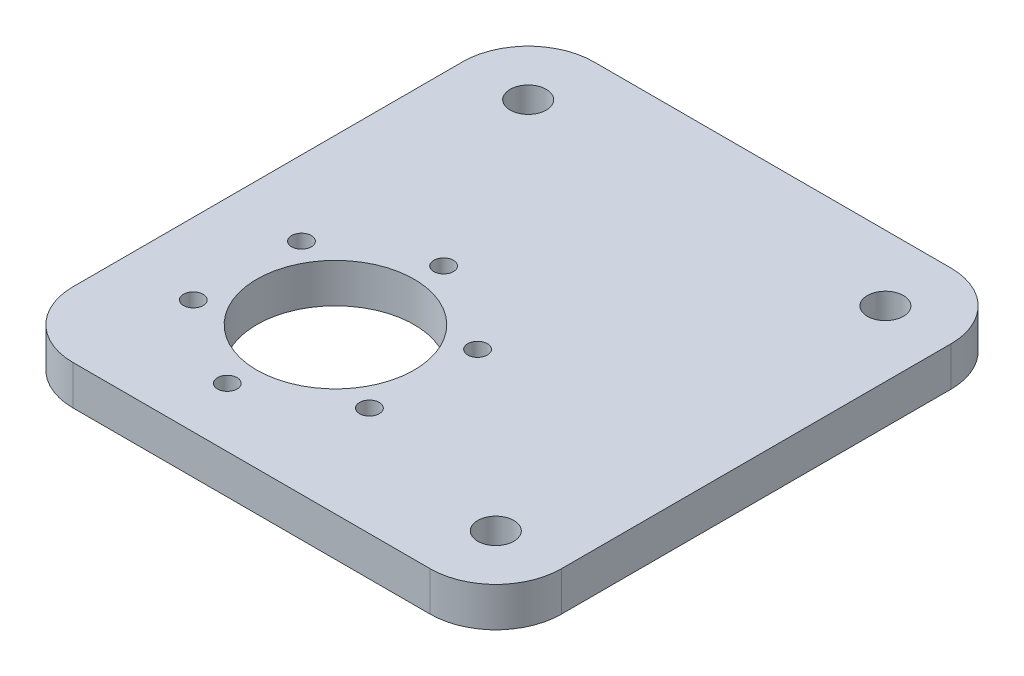
SolidWorks part; units mm, degrees
ref_plane "Front Plane" through (0, 0, 0) normal (0, 0, 1) x (1, 0, 0)
ref_plane "Top Plane" through (0, 0, 0) normal (0, 1, 0) x (1, 0, 0)
ref_plane "Right Plane" through (0, 0, 0) normal (1, 0, 0) x (0, 0, -1)
sketch "Sketch2" plane through (0, 0, 0) normal (0, 1, 0) x (1, 0, 0)
  line L1 (-18.6933, 53.5256) -> (55.7467, 53.5256)
  line L2 (-18.6933, 53.5256) -> (-18.6933, -25.8544)
  line L3 (-18.6933, -25.8544) -> (55.7467, -25.8544)
  line L4 (55.7467, 53.5256) -> (55.7467, -25.8544)
  circle A0 centre (6.3067, -0.8544) radius 12
  dimension "D1" = 24
  dimension "D2" = 74.44
  dimension "D3" = 79.38
extrude "Boss-Extrude1" add sketch "Sketch2" along normal blind 6
sketch "Sketch4" plane through (0, 6, 0) normal (0, 1, 0) x (1, 0, 0)
  circle A0 centre (367.6342, -1080.9788) radius 1.25 construction
  circle A1 centre (367.6342, -1080.9788) radius 1.25
  circle A2 centre (367.6342, -1112.9788) radius 1.25 construction
  circle A3 centre (367.6342, -1112.9788) radius 1.25
  circle A4 centre (353.7778, -1104.9788) radius 1.25 construction
  circle A5 centre (353.7778, -1104.9788) radius 1.25
  circle A6 centre (353.7778, -1104.9788) radius 1.25 construction
  circle A7 centre (353.7778, -1104.9788) radius 1.25
  circle A8 centre (353.7778, -1088.9788) radius 1.25 construction
  circle A9 centre (353.7778, -1088.9788) radius 1.25
  circle A10 centre (381.4907, -1088.9788) radius 1.25 construction
  circle A11 centre (381.4907, -1088.9788) radius 1.25
  circle A12 centre (381.4907, -1104.9788) radius 1.25 construction
  circle A13 centre (381.4907, -1104.9788) radius 1.25
sketch "Sketch6" plane through (0, 0, 0) normal (0, -1, 0) x (1, 0, 0)
  line L0 (55.7467, 25.8544) -> (55.7467, -53.5256) construction
  line L1 (55.7467, -53.5256) -> (-18.6933, -53.5256) construction
  line L2 (-18.6933, 25.8544) -> (55.7467, 25.8544) construction
  line L3 (-18.6933, -53.5256) -> (-18.6933, 25.8544) construction
  circle A0 centre (45.7467, 15.8544) radius 2.75
  circle A2 centre (45.7467, -43.5256) radius 2.75
  circle A3 centre (-8.6933, -43.5256) radius 2.75
  dimension "D5" = 5.5
  dimension "D6" = 5.5
  dimension "D7" = 5.5
  dimension "D1" = 10
  dimension "D2" = 10
  dimension "D3" = 10
  dimension "D4" = 10
extrude "Cut-Extrude2" cut sketch "Sketch6" against normal blind 10
sketch "Sketch7" plane through (0, 0, 0) normal (0, -1, 0) x (1, 0, 0)
  circle A0 centre (-7.2956, -7.5704) radius 1.25 construction
  circle A1 centre (-7.2956, -7.5704) radius 1.25
  circle A2 centre (-7.7905, 8.422) radius 1.25 construction
  circle A3 centre (-7.7905, 8.422) radius 1.25
  circle A4 centre (19.9091, 9.2791) radius 1.25 construction
  circle A5 centre (19.9091, 9.2791) radius 1.25
  circle A6 centre (20.4039, -6.7133) radius 1.25 construction
  circle A7 centre (20.4039, -6.7133) radius 1.25
  circle A8 centre (5.8119, 16.8467) radius 1.25 construction
  circle A9 centre (5.8119, 16.8467) radius 1.25
  circle A10 centre (6.8016, -15.138) radius 1.25 construction
  circle A11 centre (6.8016, -15.138) radius 1.25
sketch "Sketch8" plane through (0, 0, 0) normal (0, -1, 0) x (1, 0, 0)
  circle A0 centre (5.8119, 16.8467) radius 1.5
  circle A1 centre (19.9091, 9.2791) radius 1.5
  circle A2 centre (20.4039, -6.7133) radius 1.5
  circle A3 centre (6.8016, -15.138) radius 1.5
  circle A4 centre (-7.2956, -7.5704) radius 1.5
  circle A5 centre (-7.7905, 8.422) radius 1.5
  dimension "D1" = 3
  dimension "D2" = 3
  dimension "D3" = 3
  dimension "D4" = 3
  dimension "D5" = 3
  dimension "D6" = 3
extrude "Cut-Extrude4" cut sketch "Sketch8" against normal through all
fillet "Fillet1" radius 10 4 edges at (55.7467, 3, -53.5256) (-18.6933, 3, -53.5256) (-18.6933, 3, 25.8544) (55.7467, 3, 25.8544)
